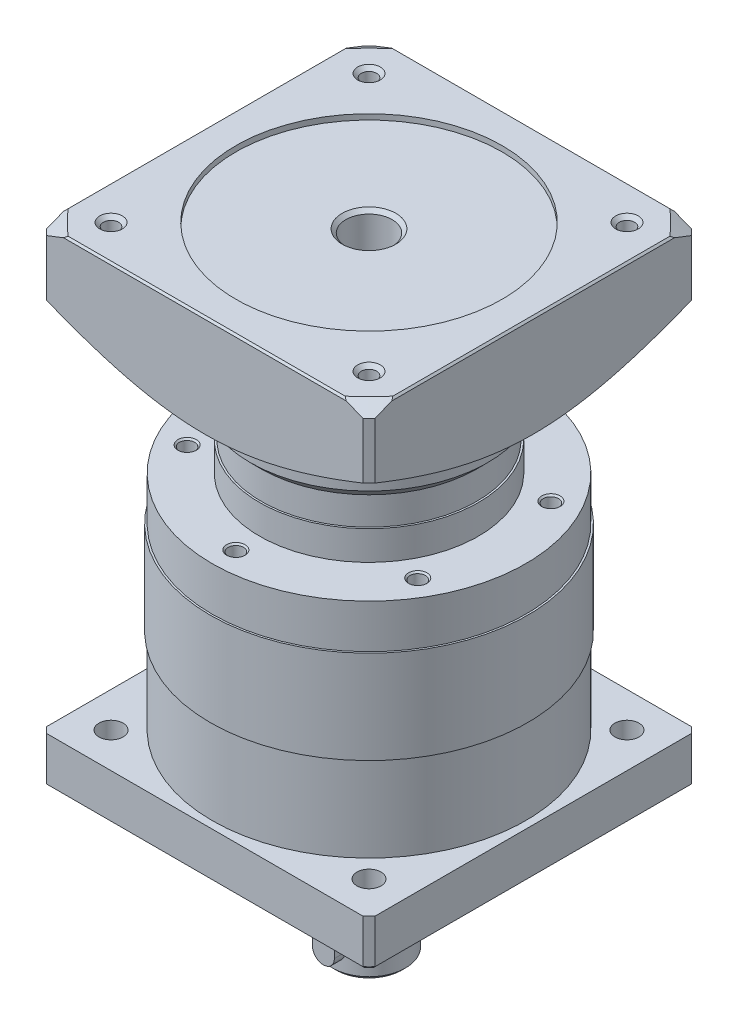
SolidWorks part; units mm, degrees
ref_plane "Спереди" through (0, 0, 0) normal (0, 0, 1) x (1, 0, 0)
ref_plane "Сверху" through (0, 0, 0) normal (0, 1, 0) x (1, 0, 0)
ref_plane "Справа" through (0, 0, 0) normal (1, 0, 0) x (0, 0, -1)
sketch "Эскиз1" plane through (0, 0, 0) normal (0, 0, 1) x (1, 0, 0)
  line L0 (0, 0) -> (0, 17.2124) construction
  line L1 (-2.1, 0) -> (-9, 0)
  line L2 (0, 17.2124) -> (0, 139.3338)
  line L3 (-36.5, 173) -> (-58.5, 173)
  line L4 (-9, 0) -> (-10, 1)
  line L5 (-62.5, 40.5) -> (-62.5, 76)
  line L6 (-39, 37) -> (-16, 37)
  line L7 (-62.5, 76) -> (-43.5, 76)
  line L9 (-10, 36) -> (-10, 1)
  line L10 (-62, 40) -> (-40, 40)
  line L11 (-6.35, 170.5) -> (-6.35, 143)
  line L12 (-62.5, 170.6906) -> (-62.5, 138)
  line L13 (-40, 40) -> (-40, 38)
  line L14 (-6.35, 143) -> (0, 139.3338)
  line L16 (-7.35, 171.5) -> (-6.35, 170.5)
  line L17 (-62.5, 138) -> (-32.5, 138)
  line L18 (-62.5, 40.5) -> (-62, 40)
  line L19 (-62.5, 170.6906) -> (-58.5, 173)
  line L20 (-40, 38) -> (-39, 37)
  line L21 (-16, 37) -> (-16, 36)
  line L22 (-16, 36) -> (-10, 36)
  line L23 (0, 17.2124) -> (-2.1, 16)
  line L24 (-2.1, 16) -> (-2.1, 0)
  line L26 (-43, 113.5) -> (-43, 101.5)
  line L27 (-32.5, 138) -> (-32.5, 129.2)
  line L28 (-32.5, 129.2) -> (-29.5, 129.2)
  line L29 (-36.5, 173) -> (-36.5, 171.5)
  line L30 (-36.5, 171.5) -> (-7.35, 171.5)
  line L31 (-43, 101.5) -> (-43.5, 101.5)
  line L32 (-43.5, 76) -> (-43.5, 101.5)
  line L33 (-29.5, 129.2) -> (-29.5, 121.5)
  line L34 (-29.5, 121.5) -> (-30, 121.5)
  line L35 (-30, 121.5) -> (-30, 113.5)
  line L36 (-30, 113.5) -> (-43, 113.5)
  point P7 (-10, 0)
  point P9 (-62.5, 40)
  point P10 (-40, 37)
  point P19 (-6.35, 171.5)
  point P30 (-2.1, 0)
  dimension "D1" = 20
  dimension "D3" = 36
  dimension "D4" = 3
  dimension "D5" = 80
  dimension "D6" = 125
  dimension "D9" = 1
  dimension "D7" = 36
  dimension "D8" = 125
  dimension "D10" = 35
  dimension "D11" = 8.8
  dimension "D14" = 0.5
  dimension "D16" = 1
  dimension "D12" = 1
  dimension "D13" = 32
  dimension "D17" = 4.2
  dimension "D18" = 16
  dimension "D19" = 60
  dimension "D20" = 86
  dimension "D21" = 65
  dimension "D15" = 0.5
  dimension "D23" = 60
  dimension "D24" = 30
  dimension "D25" = 12.7
  dimension "D26" = 25.5
  dimension "D35" = 12
  dimension "D27" = 1.5
  dimension "D28" = 73
  dimension "D32" = 1
  dimension "D30" = 30
  dimension "D31" = 117
  dimension "D33" = 40
  dimension "D34" = 173
  dimension "D36" = 7.7
  dimension "D37" = 15.7
  dimension "D38" = 0.5
  dimension "D39" = 59
  dimension "D40" = 3
  dimension "D41" = 8
revolve "Повернуть1" add sketch "Эскиз1" angle 360 about L0
sketch "Эскиз2" plane through (0, 40, 0) normal (0, -1, 0) x (1, 0, 0)
  line L1 (45, 45) -> (-45, 45)
  line L2 (-45, 45) -> (-45, -45)
  line L3 (-45, -45) -> (45, -45)
  line L4 (45, -45) -> (45, 45)
  circle A0 centre (0, 0) radius 45 construction
  dimension "D1" = 90
extrude "Вырез-Вытянуть1" cut sketch "Эскиз2" against normal through all flip side to cut
sketch "Эскиз3" plane through (0, 40, 0) normal (0, -1, 0) x (1, 0, 0)
  line L0 (-35.3553, 35.3553) -> (0, 0) construction
  line L1 (0, 0) -> (-39, 0) construction
  circle A0 centre (-35.3553, 35.3553) radius 3.3
  circle A1 centre (35.3553, 35.3553) radius 3.3
  circle A2 centre (35.3553, -35.3553) radius 3.3
  circle A3 centre (-35.3553, -35.3553) radius 3.3
  circle A4 centre (0, 0) radius 39 construction
  dimension "D1" = 6.6
  dimension "D2" = 45
  dimension "D3" = 50
extrude "Вырез-Вытянуть2" cut sketch "Эскиз3" against normal blind 34.5
chamfer "Фаска1" distance 0.3 angle 45 4 edges at (35.3553, 40, 32.0553) (35.3553, 40, -38.6553) (-35.3553, 40, -38.6553) (-35.3553, 40, 32.0553)
chamfer "Фаска2" distance 0.5 angle 45 4 edges at (-45, 40, 0) (0, 40, -45) (45, 40, 0) (0, 40, 45)
chamfer "Фаска3" distance 0.5 angle 45 4 edges at (0, 173, -45) (-45, 173, 0) (0, 173, 45) (45, 173, 0)
sketch "Эскиз5" plane through (0, 0, 0) normal (0, 0, 1) x (1, 0, 0)
  line L0 (-3, 30) -> (-3, 6)
  line L1 (3, 30) -> (3, 6)
  line L3 (-9, 0) -> (9, 0) construction
  arc A0 (3, 30) -> (-3, 30) centre (0, 30) ccw
  arc A1 (-3, 6) -> (3, 6) centre (0, 6) ccw
  dimension "D1" = 3
  dimension "D2" = 6
  dimension "D3" = 30
sketch "Эскиз8" plane through (0, 76, 0) normal (0, 1, 0) x (1, 0, 0)
  circle A0 centre (0, 0) radius 43
  dimension "D1" = 86
extrude "Вырез-Вытянуть6" cut sketch "Эскиз8" against normal blind 23.5 flip side to cut
extrude "Вытянуть1" add sketch "Эскиз5" against normal up to surface (2.9606 mm away) from offset 12.5 up to face at (0, 1, -10)
sketch "Эскиз7" plane through (0, 138, 0) normal (0, 1, 0) x (1, 0, 0)
  line L0 (-27.4767, 37.4767) -> (-27.4767, 62.6701)
  line L2 (-27.4767, 62.6701) -> (-56.8781, 62.6701)
  line L3 (-37.4767, 27.4767) -> (-56.8781, 27.4767)
  line L4 (-56.8781, 27.4767) -> (-56.8781, 62.6701)
  line L17 (0, 0) -> (-37.4767, 37.4767) construction
  line L18 (0, 0) -> (-44.5, 0) construction
  line L19 (-44.5, 37.9737) -> (-44.5, -37.9737) construction
  arc A0 (-37.4767, 27.4767) -> (-27.4767, 37.4767) centre (-37.4767, 37.4767) ccw
  dimension "D3" = 20
  dimension "D1" = 45
  dimension "D2" = 53
ref_plane "Плоскость1" through (-45, 52.5, -43.3734) normal (0, 0, -1) x (-1, 0, 0)
sketch "Эскиз10" plane through (0, 173, 0) normal (0, 1, 0) x (1, 0, 0)
  line L0 (-35.3553, 35.3553) -> (0, 0) construction
  line L1 (0, 0) -> (-44.5, 0) construction
  line L2 (-44.5, 37.9737) -> (-44.5, -37.9737) construction
  circle A0 centre (-35.3553, 35.3553) radius 2.1
  dimension "D3" = 4.2
  dimension "D1" = 45
  dimension "D2" = 50
extrude "Вырез-Вытянуть8" cut sketch "Эскиз10" against normal blind 20
chamfer "Фаска4" distance 1 angle 45 1 edges at (-35.3553, 173, -33.2553)
pattern_circular "Круговой массив1" count 4 over 360 about axis through (0, 0, 0) along (0, 1, 0) of "Фаска4", "Вырез-Вытянуть8"
sketch "Эскиз11" plane through (0, 171.5, 0) normal (0, 1, 0) x (1, 0, 0)
  line L1 (-3, 4) -> (3, 4)
  line L2 (-3, 4) -> (-3, -1.8541)
  line L3 (-3, -1.8541) -> (3, -1.8541)
  line L4 (3, 4) -> (3, -1.8541)
  dimension "D1" = 6
  dimension "D2" = 3
  dimension "D3" = 4
chamfer "Фаска5" distance 3 angle 45 1 edges at (0, 129.2, -32.5)
ref_plane "Плоскость2" through (0, 0, 0) normal (0.7071, 0, -0.7071) x (-0.7071, 0, -0.7071)
sketch "Эскиз12" plane through (0, 0, 0) normal (0.7071, 0, -0.7071) x (-0.7071, 0, -0.7071)
  line L0 (-32.5, 138) -> (-62.9894, 155.6031)
  line L1 (-62.4894, 170.6906) -> (-62.4894, 138) construction
  line L2 (-62.4894, 155.3144) -> (-62.4894, 138) construction
  line L3 (-62.9894, 138) -> (-32.5, 138)
  line L4 (-62.9894, 155.6031) -> (-62.9894, 138)
  line L5 (-32.5, 138) -> (32.5, 138) construction
  dimension "D1" = 30
  dimension "D2" = 0.5
revolve "Вырез-Повернуть1" cut sketch "Эскиз12" angle 360 about axis through (0, 0, 0) along (0, -1, 0)
sketch "Эскиз13" plane through (0, 113.5, 0) normal (0, 1, 0) x (1, 0, 0)
  line L1 (0, -36.5) -> (31.6099, -18.25) construction
  line L2 (31.6099, -18.25) -> (31.6099, 18.25) construction
  line L3 (31.6099, 18.25) -> (0, 36.5) construction
  line L4 (0, 36.5) -> (-31.6099, 18.25) construction
  line L5 (-31.6099, 18.25) -> (-31.6099, -18.25) construction
  line L6 (-31.6099, -18.25) -> (0, -36.5) construction
  circle A0 centre (0, 0) radius 36.5 construction
  circle A2 centre (0, 0) radius 30 construction
  circle A3 centre (0, 0) radius 30 construction
  circle A4 centre (0, 0) radius 43 construction
  dimension "D1" = 13
  dimension "D2" = 6.5
hole_wizard "Отверстие обработанное метчиком M5x0.81" positions "Трехмерный эскиз1" profile "Эскиз14" tap size "M5x0.8" standard "ГОСТ"
sketch3d "Трехмерный эскиз1"
  point P0 (0, 113.5, 36.5)
  point P3 (31.6099, 113.5, 18.25)
  point P6 (31.6099, 113.5, -18.25)
  point P9 (0, 113.5, -36.5)
  point P12 (-31.6099, 113.5, -18.25)
  point P15 (-31.6099, 113.5, 18.25)
sketch "Эскиз14" plane through (0, 113.5, 36.5) normal (1, 0, 0) x (0, 0, 1)
  line L0 (0, 0) -> (0, 15.2618)
  line L1 (0, 15.2618) -> (2.1, 14)
  line L2 (2.1, 14) -> (2.1, 0.425)
  line L3 (2.1, 0.425) -> (2.525, 0)
  line L5 (2.525, 0) -> (0, 0)
  line L6 (-2.1, 0.425) -> (-2.525, 0) construction
  line L10 (0, 15.2618) -> (-2.1, 14) construction
  line L11 (0, -6.35) -> (0, 107.95) construction
  dimension "Диаметр сверла" = 4.2
  dimension "Глубина сверла" = 14
  dimension "Диаметр передней зенковки" = 5.05
  dimension "Угол передней зенковки" = 90
  dimension "Угол заточки сверла" = 118
cosmetic thread "Отверстие резьбы1" parameters "D1"=10, "D2"=5
cosmetic thread "Отверстие резьбы2" parameters "D1"=10, "D2"=5
cosmetic thread "Отверстие резьбы3" parameters "D1"=10, "D2"=5
cosmetic thread "Отверстие резьбы4" parameters "D1"=10, "D2"=5
cosmetic thread "Отверстие резьбы5" parameters "D1"=10, "D2"=5
cosmetic thread "Отверстие резьбы6" parameters "D1"=10, "D2"=5
hole_wizard "Отверстие обработанное метчиком M6x1.01" positions "Эскиз17" profile "Эскиз16" tap size "M6x1.0" standard "ГОСТ"
sketch "Эскиз17" plane through (0, 0, 0) normal (0, -1, 0) x (1, 0, 0)
  circle A0 centre (0, 0) radius 9 construction
  point P0 (0, 0)
sketch "Эскиз16" plane through (0, 0, 0) normal (1, 0, 0) x (0, 0, -1)
  line L0 (0, 0) -> (0, 22.5022)
  line L1 (0, 22.5022) -> (2.5, 21)
  line L2 (2.5, 21) -> (2.5, 1.5)
  line L3 (2.5, 1.5) -> (4, 0)
  line L5 (4, 0) -> (0, 0)
  line L6 (-2.5, 1.5) -> (-4, 0) construction
  line L10 (0, 22.5022) -> (-2.5, 21) construction
  line L11 (0, -6.35) -> (0, 107.95) construction
  dimension "Диаметр сверла" = 5
  dimension "Глубина сверла" = 21
  dimension "Диаметр передней зенковки" = 8
  dimension "Угол передней зенковки" = 90
  dimension "Угол заточки сверла" = 118
cosmetic thread "Отверстие резьбы7" parameters "D1"=16, "D2"=6
